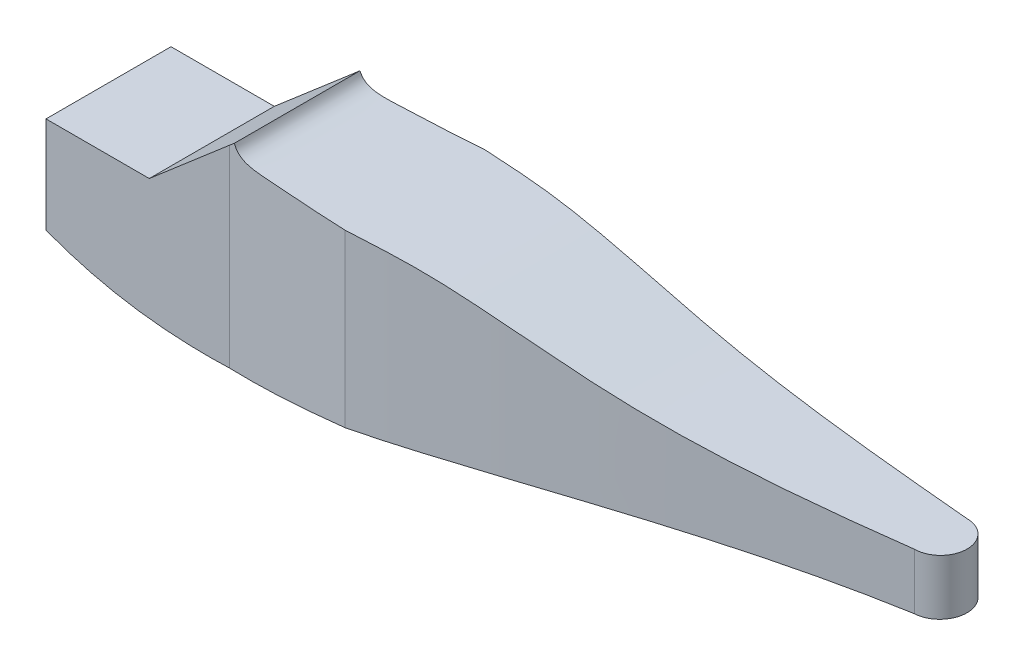
SolidWorks part; units mm, degrees
ref_plane "Front Plane" through (0, 0, 0) normal (0, 0, 1) x (1, 0, 0)
ref_plane "Top Plane" through (0, 0, 0) normal (0, 1, 0) x (1, 0, 0)
ref_plane "Right Plane" through (0, 0, 0) normal (1, 0, 0) x (0, 0, -1)
sketch "VistaInferior" plane through (0, 0, 0) normal (0, 1, 0) x (1, 0, 0)
  line L0 (-192.0637, -5.1432) -> (599.2696, -5.1432) construction
  line L1 (-378.3396, 12.2248) -> (691.3572, 12.2248) construction
ref_plane "Plane1" through (-380, 0, 0) normal (1, 0, 0) x (0, 0, -1)
sketch "VistaFrontal" plane through (-380, 0, 0) normal (1, 0, 0) x (0, 0, -1)
  line L0 (-194.9091, 33.8764) -> (208.4623, 33.8764) construction
ref_plane "Plano1" through (0, 100, 0) normal (0, 1, 0) x (1, 0, 0)
sketch "VistaSuperiorAlas" plane through (0, 100, 0) normal (0, 1, 0) x (1, 0, 0)
  line L0 (-215.3379, 28.3518) -> (575.9954, 28.3518) construction
  line L1 (-49.1326, -517.3385) -> (-49.1326, 529.3281) construction
ref_plane "Plano2" through (0, 0, 0) normal (0, 0, 1) x (1, 0, 0)
sketch "VistaLateral" plane through (0, 0, 0) normal (0, 0, 1) x (1, 0, 0)
  line L0 (-173.8902, 266.0418) -> (-35.2235, 266.0418) construction
  line L1 (-272.7691, -41.8053) -> (407.8976, -41.8053) construction
sketch "Croquis6" plane through (0, 0, 0) normal (0, 0, 1) x (1, 0, 0)
  line L0 (0, 0) -> (0, 50362.8256) construction
  line L1 (0, 0) -> (50362.8256, 0) construction
  line L2 (-389.9113, 0) -> (-389.9113, 10)
  line L3 (-389.9113, 10) -> (-314.9113, 10)
  line L4 (260.0887, 30) -> (260.0887, 0)
  line L5 (-389.9113, 0) -> (-389.9113, -60)
  line L6 (260.0887, -10) -> (260.0887, 0)
  line L7 (-314.9113, 10) -> (-252.842, 63.3427)
  spline S0 degree 3 poles (-252.842, 63.3427) (-249.5636, 53.5095) (-229.7368, 54.4566) (-175.746, 53.0624) (-106.0685, 58.5859) (54.0659, 26.7028) (176.5766, 30.1459) (260.0887, 30) knots 0 0 0 0 0.061033 0.088313 0.272805 0.517877 1 1 1 1
  spline S1 degree 3 poles (-389.9113, -60) (-298.8025, -94.9396) (-162.4707, -70.4992) (51.2931, -26.3001) (176.6655, -9.1936) (260.0887, -10) knots 0 0 0 0 0.42534 0.619702 1 1 1 1
  dimension "D1" = 30
  dimension "D2" = 10
  dimension "D3" = 10
  dimension "D4" = 60
  dimension "D5" = 75
  dimension "D7" = 650
  dimension "D22" = 70
extrude "CuerpoPrincipal" add sketch "Croquis6" along normal blind 80 and the other way blind 80
ref_plane "Plano3" through (0, 63.3427, 0) normal (0, 1, 0) x (1, 0, 0)
sketch "Croquis7" plane through (0, 63.3427, 0) normal (0, 1, 0) x (1, 0, 0)
  line L0 (-393.481, -47.7748) -> (-393.481, 43.0134)
  line L1 (-393.481, 43.0134) -> (-256.6001, 43.0134)
  line L2 (-256.6001, 43.0134) -> (-167.0057, 47.9881)
  line L3 (-393.481, -47.7748) -> (-256.6001, -47.7748)
  line L4 (-256.6001, -47.7748) -> (-167.0057, -53.3713)
  line L5 (215.8823, 15.311) -> (215.8823, -23.0283) construction
  line L7 (-495.2066, -93.407) -> (271.3348, -93.407)
  line L8 (-495.2066, -93.407) -> (-495.2066, 93.407)
  line L9 (-495.2066, 93.407) -> (271.3348, 93.407)
  line L10 (271.3348, -93.407) -> (271.3348, 93.407)
  line L11 (-495.2066, -93.407) -> (271.3348, 93.407) construction
  line L12 (-495.2066, 93.407) -> (271.3348, -93.407) construction
  arc A0 (215.8823, 15.311) -> (215.8823, -23.0283) centre (215.8823, -3.8587) cw
  spline S0 degree 2 poles (-167.0057, 47.9881) (24.5725, 33.232) (215.8823, 15.311) knots 0 0 0 1 1 1
  spline S1 degree 2 poles (-167.0057, -53.3713) (25.1388, -47.4024) (215.8823, -23.0283) knots 0 0 0 1 1 1
  point P12 (-111.9359, 0)
extrude "Cortar-Extruir3" cut sketch "Croquis7" against normal through all contours L7 L10 L9 L8 S1 L4 L3 L0 L1 L2 S0 A0 region at (-487.3168, 63.3427, 0)
